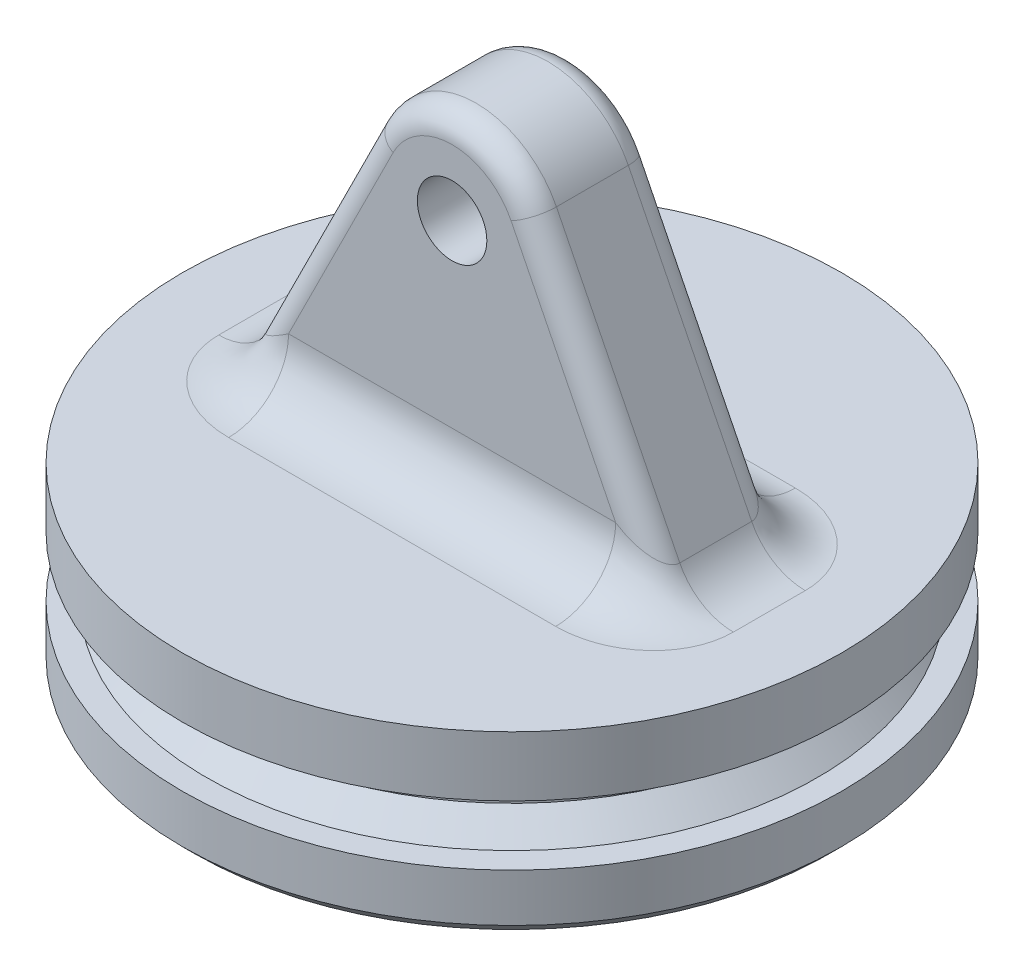
SolidWorks part; units mm, degrees
ref_plane "前基準面" through (0, 0, 0) normal (0, 0, 1) x (1, 0, 0)
ref_plane "上基準面" through (0, 0, 0) normal (0, 1, 0) x (1, 0, 0)
ref_plane "右基準面" through (0, 0, 0) normal (1, 0, 0) x (0, 0, -1)
sketch "草圖1" plane through (0, 0, 0) normal (0, 1, 0) x (1, 0, 0)
  line L1 (-18.3848, -18.3848) -> (18.3848, -18.3848)
  line L2 (-18.3848, -18.3848) -> (-18.3848, 18.3848)
  line L3 (-18.3848, 18.3848) -> (18.3848, 18.3848)
  line L4 (18.3848, -18.3848) -> (18.3848, 18.3848)
  line L5 (-18.3848, -18.3848) -> (18.3848, 18.3848) construction
  line L6 (-18.3848, 18.3848) -> (18.3848, -18.3848) construction
  point P0 (0, 0)
  dimension "D1" = 52
extrude "填料-伸長1" add sketch "草圖1" along normal blind 15
sketch "草圖2" plane through (0, 0, 0) normal (0, 0, 1) x (1, 0, 0)
  line L0 (-18.3848, 15) -> (18.3848, 15) construction
  line L1 (-6.7083, 38.354) -> (-18.3848, 15)
  line L2 (6.7083, 38.354) -> (18.3848, 15)
  line L3 (-18.3848, 15) -> (18.3848, 15)
  circle A0 centre (0, 35) radius 2.9
  arc A1 (6.7083, 38.354) -> (-6.7083, 38.354) centre (0, 35) ccw
  dimension "D1" = 5.8
  dimension "D3" = 15
  dimension "D2" = 20
extrude "填料-伸長2" add sketch "草圖2" along normal mid plane 10
sketch "草圖3" plane through (0, 0, 0) normal (0, -1, 0) x (1, 0, 0)
  circle A0 centre (0, 0) radius 27.5
  dimension "D1" = 55
extrude "填料-伸長3" add sketch "草圖3" against normal up to surface (15 mm away) up to face at (0, 15, 11.6924)
fillet "圓角1" radius 2 6 edges at (12.5465, 26.677, 5) (0, 42.5, 5) (12.5465, 26.677, -5) (0, 42.5, -5) (-12.5465, 26.677, 5) (-12.5465, 26.677, -5)
fillet "Fillet1" radius 5 8 edges at (-17.7299, 15, 4.4142) (-18.3848, 15, 0) (-17.7299, 15, -4.4142) (0, 15, -5) (17.7299, 15, -4.4142) (18.3848, 15, 0) (17.7299, 15, 4.4142) (0, 15, 5)
sketch "草圖4" plane through (0, 0, 0) normal (0, 0, 1) x (1, 0, 0)
  line L0 (-27.5, 10) -> (-23.5, 10)
  line L1 (-27.5, 15) -> (-27.5, 0) construction
  line L2 (-23.5, 10) -> (-23.5, 5)
  line L3 (-23.5, 5) -> (-27.5, 5)
  line L4 (-27.5, 5) -> (-27.5, 10)
  line L5 (0, 0) -> (0, 35) construction
  line L6 (-27.5, 15) -> (-27.5, 0)
  line L7 (28.2843, 0) -> (28.2843, 15)
  line L8 (-27.5, 7.5) -> (-23.5, 7.5) construction
  line L9 (-27.5, 15) -> (-27.5, 0) construction
  dimension "D1" = 4
  dimension "D2" = 5
revolve "除料-旋轉1" cut sketch "草圖4" angle 360 about L5
chamfer "導角2" distance 2 angle 45 2 edges at (23.5, 10, 0) (23.5, 5, 0)
chamfer "導角3" distance 1 angle 45 1 edges at (0, 0, -27.5)
